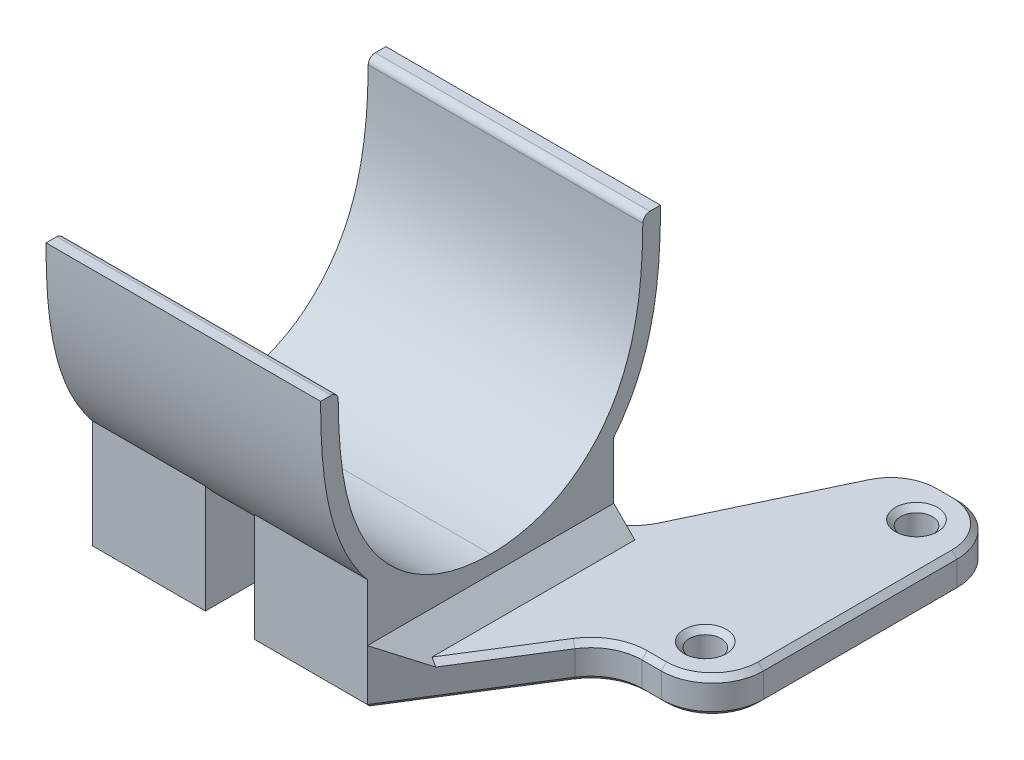
SolidWorks part; units mm, degrees
ref_plane "Front Plane" through (0, 0, 0) normal (0, 0, 1) x (1, 0, 0)
ref_plane "Top Plane" through (0, 0, 0) normal (0, 1, 0) x (1, 0, 0)
ref_plane "Right Plane" through (0, 0, 0) normal (1, 0, 0) x (0, 0, -1)
sketch "Sketch1" plane through (0, 0, 0) normal (1, 0, 0) x (0, 0, -1)
  line L0 (-21.635, -1.19) -> (-24.135, -1.19)
  line L1 (21.635, -1.19) -> (24.135, -1.19)
  spline S0 degree 3 poles (731.7054, 3883.5776) (353.3626, 1.6015) (-340.5914, -177.806) (251.198, 284.8766) (-2506.7127, -3134.9588) knots -4.832182 -4.832182 -4.832182 -4.832182 0.532714 6.099948 6.099948 6.099948 6.099948 only from (0, -31.55) to (-21.135, -1.19)
  spline S1 degree 3 poles (0, -31.55) (-8.9089, -31.55) (-20.4011, -21.9995) (-21.135, -7.0764) (-21.135, -1.19) knots 0 0 0 0 0.532714 1 1 1 1 construction
  spline S2 degree 3 poles (2506.664, -3134.8984) (-251.1944, 284.8739) (340.5877, -177.8042) (-353.3586, 1.6005) (-731.6989, 3883.5105) knots -5.099916 -5.099916 -5.099916 -5.099916 0.467286 5.832152 5.832152 5.832152 5.832152 only from (21.135, -1.19) to (0, -31.55)
  spline S3 degree 3 poles (21.135, -1.19) (21.135, -7.0764) (20.4011, -21.9995) (8.9089, -31.55) (0, -31.55) knots 0 0 0 0 0.467286 1 1 1 1 construction
  spline S4 degree 1 poles (21.635, -1.19) (0, -32.05) knots 0 0 1 1 construction
  spline S5 degree 1 poles (0, -32.05) (-21.635, -1.19) knots 0 0 1 1 construction
  spline S6 degree 3 poles (21.635, -1.19) (21.635, -1.9985) (21.6227, -3.592) (21.5101, -6.9652) (21.1304, -11.3011) (20.0604, -16.4841) (18.1161, -21.3821) (15.1187, -25.7076) (11.7777, -28.5934) (8.6068, -30.3241) (5.9868, -31.2963) (3.6015, -31.8051) (1.5867, -32.0142) (0.5246, -32.05) (0, -32.05) knots 0 0 0 0 0.0625 0.125 0.25 0.375 0.5 0.625 0.75 0.8125 0.875 0.9375 0.96875 1 1 1 1
  spline S7 degree 3 poles (0, -32.05) (-0.5246, -32.05) (-1.5867, -32.0142) (-3.6015, -31.8051) (-5.9868, -31.2963) (-8.6068, -30.3241) (-11.7777, -28.5934) (-15.1187, -25.7076) (-18.1161, -21.3821) (-20.0604, -16.4841) (-21.1304, -11.3011) (-21.5101, -6.9652) (-21.6227, -3.592) (-21.635, -1.9985) (-21.635, -1.19) knots 0 0 0 0 0.03125 0.0625 0.125 0.1875 0.25 0.375 0.5 0.625 0.75 0.875 0.9375 1 1 1 1
  spline S8 degree 1 poles (24.135, -1.19) (0, -34.55) knots 0 0 1 1 construction
  spline S9 degree 1 poles (0, -34.55) (-24.135, -1.19) knots 0 0 1 1 construction
  spline S10 degree 3 poles (24.135, -1.19) (24.135, -1.5974) (24.1319, -2.404) (24.108, -4.0826) (24.0356, -6.2451) (23.849, -8.9257) (23.4222, -12.5687) (22.4768, -17.1742) (20.3439, -22.5637) (17.0067, -27.3875) (13.2374, -30.6472) (9.6449, -32.608) (6.6822, -33.7068) (4.0029, -34.2776) (1.7556, -34.5105) (0.5813, -34.55) (0, -34.55) knots 0 0 0 0 0.03125 0.0625 0.125 0.1875 0.25 0.375 0.5 0.625 0.75 0.8125 0.875 0.9375 0.96875 1 1 1 1
  spline S11 degree 3 poles (0, -34.55) (-0.5813, -34.55) (-1.7556, -34.5105) (-4.0029, -34.2776) (-6.6822, -33.7068) (-9.6449, -32.608) (-13.2374, -30.6472) (-17.0067, -27.3875) (-20.3439, -22.5637) (-22.4768, -17.1742) (-23.4222, -12.5687) (-23.849, -8.9257) (-24.0356, -6.2451) (-24.108, -4.0826) (-24.1319, -2.404) (-24.135, -1.5974) (-24.135, -1.19) knots 0 0 0 0 0.03125 0.0625 0.125 0.1875 0.25 0.375 0.5 0.625 0.75 0.8125 0.875 0.9375 0.96875 1 1 1 1
  dimension "D1" = 0.5
  dimension "D2" = 3
extrude "Boss-Extrude1" add sketch "Sketch1" along normal mid plane 39
sketch "Sketch2" plane through (0, 0, 0) normal (0, 1, 0) x (1, 0, 0)
  line L0 (40, 162) -> (70, 132)
  line L1 (40, 132) -> (70, 162)
sketch "Sketch4" plane through (19.5, 0, 0) normal (1, 0, 0) x (0, 0, -1)
  line L0 (-17.5, -26.4315) -> (-17.5, -42.55)
  line L1 (-17.5, -42.55) -> (17.5, -42.55)
  line L2 (17.5, -42.55) -> (17.5, -26.4315)
  line L3 (0, 0) -> (0, -42.55) construction
  spline S0 degree 3 poles (-108.9539, 1996.8843) (-17.9629, 18.1788) (-24.452, 20.131) (-24.108, -4.0826) (-24.0356, -6.2451) (-23.849, -8.9257) (-23.4222, -12.5687) (-22.4768, -17.1742) (-20.3439, -22.5637) (-17.0067, -27.3875) (-13.2374, -30.6472) (-9.6449, -32.608) (-6.6822, -33.7068) (-4.0029, -34.2776) (25.1625, -37.2994) (84.7325, 7.6887) (-1990.086, 160.1545) knots -1.678133 -1.678133 -1.678133 -1.678133 0.03125 0.0625 0.125 0.1875 0.25 0.375 0.5 0.625 0.75 0.8125 0.875 0.9375 0.96875 2.497229 2.497229 2.497229 2.497229 only from (-24.135, -1.19) to (0, -34.55) construction
  spline S1 degree 3 poles (1990.0533, 160.1521) (-84.7319, 7.6882) (-25.1624, -37.2994) (4.0029, -34.2776) (6.6822, -33.7068) (9.6449, -32.608) (13.2374, -30.6472) (17.0067, -27.3875) (20.3439, -22.5637) (22.4768, -17.1742) (23.4222, -12.5687) (23.849, -8.9257) (24.0356, -6.2451) (24.108, -4.0826) (24.452, 20.1311) (17.9628, 18.1788) (108.9558, 1996.9257) knots -1.497221 -1.497221 -1.497221 -1.497221 0.03125 0.0625 0.125 0.1875 0.25 0.375 0.5 0.625 0.75 0.8125 0.875 0.9375 0.96875 2.678145 2.678145 2.678145 2.678145 only from (0, -34.55) to (24.135, -1.19) construction
  spline S2 degree 3 poles (-17.5, -26.4315) (-17.2761, -26.7042) (-15.7715, -28.4557) (-13.2374, -30.6472) (-9.6449, -32.608) (-6.6822, -33.7068) (-4.0029, -34.2776) (-1.7556, -34.5105) (-0.5813, -34.55) (0, -34.55) knots 0.602407 0.602407 0.602407 0.602407 0.625 0.75 0.8125 0.875 0.9375 0.96875 1 1 1 1
  spline S3 degree 3 poles (0, -34.55) (0.5813, -34.55) (1.7556, -34.5105) (4.0029, -34.2776) (6.6822, -33.7068) (9.6449, -32.608) (13.2374, -30.6472) (15.7715, -28.4557) (17.2761, -26.7042) (17.5, -26.4315) knots 0 0 0 0 0.03125 0.0625 0.125 0.1875 0.25 0.375 0.397593 0.397593 0.397593 0.397593
  dimension "D1" = 35
  dimension "D2" = 8
extrude "Boss-Extrude2" add sketch "Sketch4" against normal up to surface (39 mm away) up to face at (-19.5, -11.8933, 0.4167)
sketch "Sketch5" plane through (0, -42.55, 0) normal (0, -1, 0) x (1, 0, 0)
  line L0 (0, 0) -> (55, 0) construction
  line L1 (55, 0) -> (55, -25) construction
  line L3 (40, -40) -> (70, -10)
  line L4 (70, -40) -> (40, -10)
  line L5 (40, -162) -> (70, -132) construction
  line L6 (40, -132) -> (70, -162) construction
  point P6 (55, -25)
  point P10 (55, -25)
  dimension "D1" = 25
  dimension "D2" = 55
  dimension "D3" = 45
sketch "Sketch11" plane through (0, -42.55, 0) normal (0, -1, 0) x (1, 0, 0)
  line L0 (33, -4) -> (19.5, 17.5)
  line L1 (33, -4) -> (47, -4)
  line L2 (33, -4) -> (33, -46) construction
  line L3 (33, -46) -> (47, -46)
  line L4 (47, -4) -> (47, -46)
  line L5 (19.5, 17.5) -> (19.5, -17.5)
  line L6 (19.5, -17.5) -> (33, -46)
  line L7 (33, -40) -> (47, -40) construction
  line L8 (33, -10) -> (47, -10) construction
  line L9 (55, -25) -> (47, -25) construction
  dimension "D1" = 14
  dimension "D2" = 42
extrude "Boss-Extrude4" add sketch "Sketch11" against normal blind 5
fillet "Fillet2" radius 7.25 5 edges at (33, -40.05, -46) (47, -40.05, -46) (33, -40.05, -4) (47, -40.05, -4) (19.5, -40.05, -17.5)
hole_wizard "#8 Clearance Hole2" positions "Sketch12" profile "Sketch13" hole size "#8" standard "ANSI Inch" end condition through all
sketch "Sketch12" plane through (0, -37.55, 0) normal (0, 1, 0) x (1, 0, 0)
  point P0 (40, 40)
  point P3 (40, 10)
sketch "Sketch13" plane through (40, -37.55, -40) normal (1, 0, 0) x (0, 0, 1)
  line L0 (0, 0) -> (0, 5)
  line L1 (0, 5) -> (2.2479, 5)
  line L2 (2.2479, 5) -> (2.2479, 0)
  line L5 (2.2479, 0) -> (0, 0)
  line L11 (0, -6.35) -> (0, 107.95) construction
  dimension "Thru Hole Dia." = 4.4958
  dimension "Thru Hole Depth" = 5
sketch "Sketch14" plane through (0, 0, 0) normal (1, 0, 0) x (0, 0, -1)
  line L0 (-17.5, -42.55) -> (-17.5, -26.4315)
  line L1 (-17.5, -42.55) -> (-17.5, -26.4315) construction
  line L2 (-17.5, -42.55) -> (17.5, -42.55)
  line L3 (17.5, -42.55) -> (17.5, -26.4315)
  line L4 (17.5, -26.4315) -> (17.5, -42.55) construction
  spline S0 degree 3 poles (108.9539, 1996.8843) (17.9629, 18.1788) (24.452, 20.131) (24.108, -4.0826) (24.0356, -6.2451) (23.849, -8.9257) (23.4222, -12.5687) (22.4768, -17.1742) (20.3439, -22.5637) (17.0067, -27.3875) (13.2374, -30.6472) (9.6449, -32.608) (6.6822, -33.7068) (4.0029, -34.2776) (-25.1625, -37.2994) (-84.7325, 7.6887) (1990.086, 160.1545) knots -1.678133 -1.678133 -1.678133 -1.678133 0.03125 0.0625 0.125 0.1875 0.25 0.375 0.5 0.625 0.75 0.8125 0.875 0.9375 0.96875 2.497229 2.497229 2.497229 2.497229 only from (24.135, -1.19) to (0, -34.55) construction
  spline S1 degree 3 poles (-1990.0533, 160.1521) (84.7319, 7.6882) (25.1624, -37.2994) (-4.0029, -34.2776) (-6.6822, -33.7068) (-9.6449, -32.608) (-13.2374, -30.6472) (-17.0067, -27.3875) (-20.3439, -22.5637) (-22.4768, -17.1742) (-23.4222, -12.5687) (-23.849, -8.9257) (-24.0356, -6.2451) (-24.108, -4.0826) (-24.452, 20.1311) (-17.9628, 18.1788) (-108.9558, 1996.9257) knots -1.497221 -1.497221 -1.497221 -1.497221 0.03125 0.0625 0.125 0.1875 0.25 0.375 0.5 0.625 0.75 0.8125 0.875 0.9375 0.96875 2.678145 2.678145 2.678145 2.678145 only from (0, -34.55) to (-24.135, -1.19) construction
  spline S2 degree 3 poles (17.5, -26.4315) (17.2761, -26.7042) (15.7715, -28.4557) (13.2374, -30.6472) (9.6449, -32.608) (6.6822, -33.7068) (4.0029, -34.2776) (1.7556, -34.5105) (0.5813, -34.55) (0, -34.55) knots 0.602407 0.602407 0.602407 0.602407 0.625 0.75 0.8125 0.875 0.9375 0.96875 1 1 1 1
  spline S3 degree 3 poles (0, -34.55) (-0.5813, -34.55) (-1.7556, -34.5105) (-4.0029, -34.2776) (-6.6822, -33.7068) (-9.6449, -32.608) (-13.2374, -30.6472) (-15.7715, -28.4557) (-17.2761, -26.7042) (-17.5, -26.4315) knots 0 0 0 0 0.03125 0.0625 0.125 0.1875 0.25 0.375 0.397593 0.397593 0.397593 0.397593
extrude "Cut-Extrude3" cut sketch "Sketch14" against normal mid plane 7
sketch "Sketch15" plane through (0, -42.55, 0) normal (0, -1, 0) x (1, 0, 0)
  line L0 (-19.5, 14.67) -> (-11.775, 14.67)
  line L1 (-19.5, -17.5) -> (-19.5, 17.5) construction
  line L2 (-11.775, 4.67) -> (-19.5, 4.67)
  line L3 (-19.5, 4.67) -> (-19.5, 14.67)
  circle A0 centre (-11.775, 9.67) radius 3.125 construction
  circle A1 centre (-11.775, 9.67) radius 3.125 construction
  arc A2 (-11.775, 14.67) -> (-11.775, 4.67) centre (-11.775, 9.67) cw
  dimension "D1" = 10
extrude "Cut-Extrude4" cut sketch "Sketch15" against normal through all
chamfer "Chamfer1" distance 3 angle 45 1 edges at (19.5, -37.55, 0)
chamfer "Chamfer2" distance 0.75 angle 45 35 edges at (-19.5, -42.55, 16.085) (-11.5, -42.55, 17.5) (-3.5, -42.55, 0) (-11.5, -42.55, -17.5) (-19.5, -42.55, -6.415) (-15.6375, -42.55, 4.67) (-6.775, -42.55, 9.67) (-15.6375, -42.55, 14.67) (40, -42.55, -12.2479) (40, -42.55, -42.2479) (11.5, -42.55, 17.5) (25.1842, -42.55, 8.4473) (33.5005, -42.55, -3.0948) (38.3792, -42.55, -4) (44.8765, -42.55, -6.1235) (47, -42.55, -25) (44.8765, -42.55, -43.8765) (38.669, -42.55, -46) (33.7111, -42.55, -44.8763) (26.25, -42.55, -31.75) (9.206, -42.55, -17.5) (3.5, -42.55, 0) (40, -37.55, -37.7521) (26.25, -37.55, -31.75) (33.7111, -37.55, -44.8763) (38.669, -37.55, -46) (44.8765, -37.55, -43.8765) (47, -37.55, -25) (26.6842, -37.55, 6.0585) (44.8765, -37.55, -6.1235) (33.5005, -37.55, -3.0948) (38.3792, -37.55, -4) (40, -37.55, -7.7521) (18.7889, -42.55, -18.6237) (18.7889, -37.55, -18.6237)
fillet "Fillet3" radius 1 2 edges at (0, -1.19, -21.635) (0, -1.19, 21.635)
